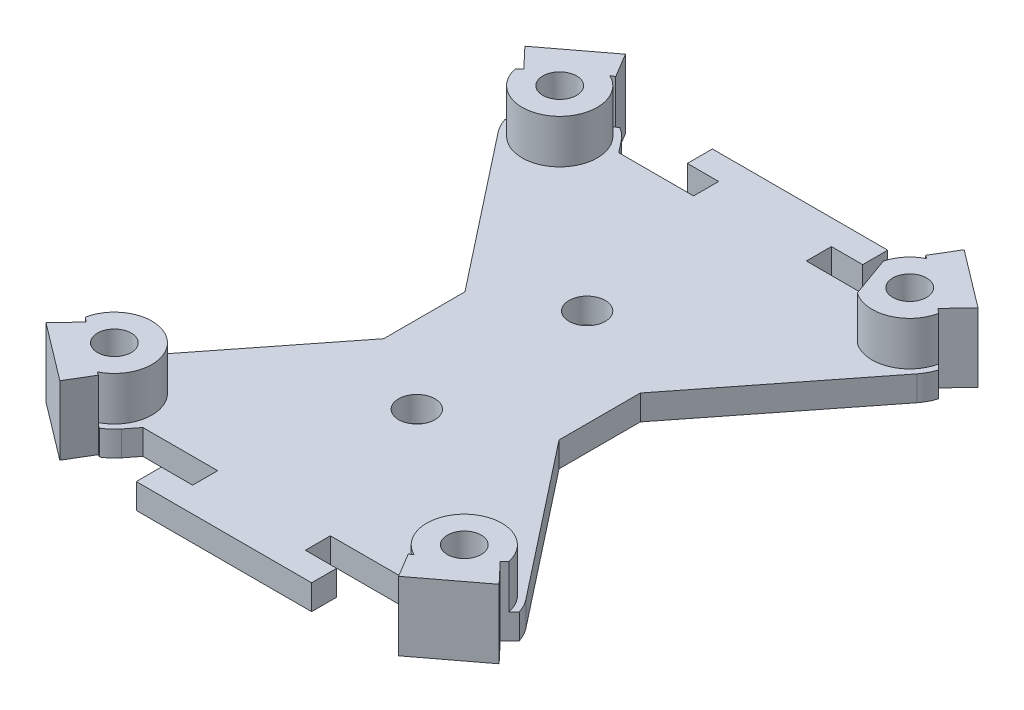
SolidWorks part; units mm, degrees
note: '?' marks a value the reader was unsure of. The reader was unsure of these and kept them because the rebuilt part matched: shared geometry of "Sketch1<3>", "Sketch1<5>".
ref_plane "Front Plane" through (0, 0, 0) normal (0, 0, 1) x (1, 0, 0)
ref_plane "Top Plane" through (0, 0, 0) normal (0, 1, 0) x (1, 0, 0)
ref_plane "Right Plane" through (0, 0, 0) normal (1, 0, 0) x (0, 0, -1)
sketch "Sketch1" plane through (0, 0, 0) normal (0, 1, 0) x (1, 0, 0)
  line L0 (0, 0) -> (0, 50000) construction
  line L1 (-13.97, 17.78) -> (13.97, 17.78) construction
  line L2 (-13.97, 17.78) -> (-13.97, -17.78) construction
  line L3 (-13.97, -17.78) -> (13.97, -17.78) construction
  line L4 (13.97, 17.78) -> (13.97, -17.78) construction
  line L5 (-13.97, 17.78) -> (13.97, -17.78) construction
  line L6 (-13.97, -17.78) -> (13.97, 17.78) construction
  line L7 (0, 0) -> (50000, 0) construction
  line L8 (0, 0) -> (18.0898, 19.1183)
  line L9 (18.0898, 19.1183) -> (13.523, 22.5805)
  line L10 (0, 0) -> (13.523, 22.5805)
  line L20 (15.8064, 20.8494) -> (16.0519, 21.1733) construction
  line L21 (-16.5, -20.62) -> (16.5, -20.62) construction
  line L22 (-16.5, -20.62) -> (-16.5, 20.62) construction
  line L23 (-16.5, 20.62) -> (16.5, 20.62) construction
  line L24 (16.5, -20.62) -> (16.5, 20.62) construction
  line L25 (-16.5, -20.62) -> (16.5, 20.62) construction
  line L26 (-16.5, 20.62) -> (16.5, -20.62) construction
  line L27 (18.0898, 19.1183) -> (18.2616, 19.2999) construction
  line L28 (0, 0) -> (13.523, -22.5805)
  line L29 (18.0898, -19.1183) -> (13.523, -22.5805)
  line L30 (0, 0) -> (18.0898, -19.1183)
  line L31 (0, 0) -> (-13.523, 22.5805)
  line L32 (-18.0898, 19.1183) -> (-13.523, 22.5805)
  line L33 (0, 0) -> (-18.0898, 19.1183)
  line L34 (0, 0) -> (-18.0898, -19.1183)
  line L35 (-18.0898, -19.1183) -> (-13.523, -22.5805)
  line L36 (0, 0) -> (-13.523, -22.5805)
  circle A0 centre (0, 0) radius 24.07
  circle A1 centre (0, 0) radius 26.5702 construction
  circle A6 centre (0, 0) radius 34.3136
  dimension "D1" = 48.14
  dimension "D8" = 53.1403
  dimension "D2" = 27.94
  dimension "D3" = 35.56
  dimension "D4" = 33
  dimension "D5" = 41.24
  dimension "D6" = 4.75
  dimension "D7" = 7.75
  dimension "D9" = 0.25
extrude "Boss-Extrude1" add sketch "Sketch1" along normal blind 2 contours L33 A0 L34 | L10 A0 L31 | L30 A0 L8 | L36 A0 L28 | L28 A0 L30 | L34 A0 L36 | L31 A0 L33 | L8 A0 L10
extrude "Boss-Extrude2" add sketch "Sketch1<3>" along normal offset from surface (5.5 mm away) 3.5 contours A0 L31 L32 L33 | A0 L8 L9 L10 | A0 L28 L29 L30 | A0 L34 L35 L36
sketch "Sketch1<3>" plane through (0, 0, 0) normal (0, 1, 0) x (1, 0, 0) same geometry as "Sketch1"
sketch "Sketch2" plane through (0, 0, 0) normal (0, 1, 0) x (1, 0, 0)
  line L4 (0, -200000) -> (0, 250000) construction
  line L5 (-200000, 0) -> (250000, 0) construction
  line L7 (0, -200000) -> (0, 250000)
  line L8 (-200000, 0) -> (250000, 0)
  circle A14 centre (13.97, 17.78) radius 3
  circle A15 centre (13.97, -17.78) radius 3
  circle A25 centre (-13.97, -17.78) radius 3
  circle A26 centre (-13.97, 17.78) radius 3
  dimension "D1" = 6
extrude "Boss-Extrude5" add sketch "Sketch2" along normal up to surface (5.5 mm away) up to face at (15.1524, 5.5, 19.9867)
ref_axis "Axis1" through (13.97, 0, -17.78) along (0, 1, 0)?
ref_axis "Axis2" through (-13.97, 0, 17.78) along (0, 1, 0)?
ref_plane "Plane1" through (0, 0, 0) normal (-0.7863, 0, -0.6178) x (-0.6178, 0, 0.7863)
sketch "Sketch3" plane through (0, 0, 0) normal (-0.7863, 0, -0.6178) x (-0.6178, 0, 0.7863)
  line L0 (19.6117, 0) -> (26.2093, 3.8091)
  line L1 (26.4079, 0) -> (6.0198, 0) construction
  line L2 (26.2093, 5.5) -> (26.2093, 0) construction
  line L3 (0, 0) -> (26.1103, 0) construction
  line L4 (19.6117, 0) -> (26.2093, 0)
  line L5 (26.2093, -3.8091) -> (26.2093, 3.8091)
  line L6 (19.6117, 5.5) -> (19.6117, 2) construction
  line L7 (0, 0) -> (0, 50000) construction
  line L8 (-26.2093, -3.8091) -> (-26.2093, 3.8091)
  line L9 (-19.6117, 0) -> (-26.2093, 0)
  line L10 (-19.6117, 0) -> (-26.2093, 3.8091)
  line L11 (-19.6117, 0) -> (-26.2093, -3.8091)
  line L12 (19.6117, 0) -> (26.2093, -3.8091)
  dimension "D1" = 30
extrude "Boss-Extrude6" [suppressed] add sketch "Sketch3" along normal up to vertex and the other way up to vertex contours L4 L12 L5 | L11 L9 L8
mirror "Mirror1" [suppressed] about plane through (0, 0, 0) normal (1, 0, 0)
extrude "Cut-Extrude3" cut sketch "Sketch1<5>" along normal through all both and the other way through all contours A6 A0 L30 L29 L28 L36 L35 L34 L33 L32 L31 L10 L9 L8
sketch "Sketch1<5>" plane through (0, 0, 0) normal (0, 1, 0) x (1, 0, 0) same geometry as "Sketch1"
hole_wizard "M2.5 Clearance Hole1" positions "Sketch6" profile "Sketch7" hole size "M2.5" standard "ANSI Metric" end condition through all
sketch "Sketch6" plane through (0, 5.5, 0) normal (0, 1, 0) x (1, 0, 0)
  point P0 (-13.97, 17.78)
  point P3 (13.97, 17.78)
  point P6 (13.97, -17.78)
  point P9 (-13.97, -17.78)
sketch "Sketch7" plane through (-13.97, 5.5, -17.78) normal (1, 0, 0) x (0, 0, 1)
  line L0 (0, 0) -> (0, 5.5005)
  line L1 (0, 5.5005) -> (1.35, 5.5005)
  line L2 (1.35, 5.5005) -> (1.35, 0)
  line L5 (1.35, 0) -> (0, 0)
  line L11 (0, -6.35) -> (0, 107.95) construction
  dimension "Thru Hole Dia." = 2.7
  dimension "Thru Hole Depth" = 5.5005
sketch "Sketch8" plane through (0, 0, 0) normal (0, -1, 0) x (1, 0, 0)
  line L0 (-13.97, 17.78) -> (13.97, -17.78) construction
  line L1 (-11.2179, 19.9424) -> (16.7221, -15.6176)
  line L2 (-16.7221, 15.6176) -> (11.2179, -19.9424)
  line L3 (13.97, 17.78) -> (-13.97, -17.78) construction
  line L4 (16.7221, 15.6176) -> (-11.2179, -19.9424)
  line L5 (11.2179, 19.9424) -> (-16.7221, -15.6176)
  line L6 (-7, -23) -> (-7, -21)
  line L7 (-7, -23) -> (7, -23)
  line L8 (0, 0) -> (0, 50000) construction
  line L9 (0, 0) -> (50000, 0) construction
  line L10 (-7, -21) -> (-4.5, -21)
  line L11 (-4.5, -21) -> (-4.5, -19)
  line L12 (-4.5, -19) -> (-10.4774, -19)
  line L13 (4.5, -19) -> (10.4774, -19)
  line L14 (4.5, -21) -> (4.5, -19)
  line L15 (7, -21) -> (4.5, -21)
  line L16 (7, -23) -> (7, -21)
  line L17 (7, 23) -> (7, 21)
  line L18 (7, 21) -> (4.5, 21)
  line L19 (4.5, 21) -> (4.5, 19)
  line L20 (4.5, 19) -> (10.4774, 19)
  line L21 (-4.5, 19) -> (-10.4774, 19)
  line L22 (-4.5, 21) -> (-4.5, 19)
  line L23 (-7, 21) -> (-4.5, 21)
  line L24 (-7, 23) -> (7, 23)
  line L25 (-7, 23) -> (-7, 21)
  line L26 (-7, -3.244) -> (-7, 3.244)
  line L27 (7, -3.244) -> (7, 3.244)
  arc A0 (-11.2179, 19.9424) -> (-16.7221, 15.6176) centre (-13.97, 17.78) ccw
  arc A1 (11.2179, -19.9424) -> (16.7221, -15.6176) centre (13.97, -17.78) ccw
  arc A2 (16.7221, 15.6176) -> (11.2179, 19.9424) centre (13.97, 17.78) ccw
  arc A3 (-16.7221, -15.6176) -> (-11.2179, -19.9424) centre (-13.97, -17.78) ccw
  circle A4 centre (0, 0) radius 34.9219
  point P4 (0, 0)
  point P9 (0, 0)
  point P27 (0, 23)
  point P32 (0, -23)
  point P39 (0, -23)
  point P50 (-7, 0)
  arc M14 (16.5433, -17.4839) -> (16.5433, 17.4839) centre (0, 0) ccw
  arc M18 (12.3669, 20.65) -> (-12.3669, 20.65) centre (0, 0) ccw
  arc M22 (-16.5433, 17.4839) -> (-16.5433, -17.4839) centre (0, 0) ccw
  arc M26 (-12.3669, -20.65) -> (12.3669, -20.65) centre (0, 0) ccw
  dimension "D1" = 7
  dimension "D2" = 7
  dimension "D3" = 23
  dimension "D4" = 2
  dimension "D5" = 2
  dimension "D6" = 2.5
  dimension "D7" = 7
extrude "Cut-Extrude4" cut sketch "Sketch8" against normal through all contours A4 A3 A0 A2 A1 M22 M18 M14 M26 | A3 L5 L2 A0 M22 | A2 A0 L1 L5 M18 | A2 L4 L1 A1 M14 | A3 A1 L2 L4 M26
ref_plane "Plane2" [suppressed] through (0, 2, 0) normal (0, 1, 0) x (1, 0, 0)
other "SurfaceCut1" [suppressed]
sketch "Sketch9" plane through (0, 0, 0) normal (0, 1, 0) x (1, 0, 0)
  line L44 (11, -14) -> (3.5, -4.4545)
  line L45 (3.5, -4.4545) -> (3.5, -14)
  line L46 (3.5, -14) -> (11, -14)
  line L47 (10.4774, -19) -> (4.5, -19) construction
  line L48 (7, -3.244) -> (16.7221, -15.6176) construction
  line L49 (0, 0) -> (0, 50000) construction
  line L50 (0, 0) -> (50000, 0) construction
  line L51 (-3.5, -14) -> (-11, -14)
  line L52 (-3.5, -4.4545) -> (-3.5, -14)
  line L53 (-11, -14) -> (-3.5, -4.4545)
  line L54 (3.5, 14) -> (11, 14)
  line L55 (3.5, 4.4545) -> (3.5, 14)
  line L56 (11, 14) -> (3.5, 4.4545)
  line L57 (-11, 14) -> (-3.5, 4.4545)
  line L58 (-3.5, 4.4545) -> (-3.5, 14)
  line L59 (-3.5, 14) -> (-11, 14)
  dimension "D1" = 5
  dimension "D2" = 3.5
  dimension "D3" = 3.5
extrude "Cut-Extrude5" [suppressed] cut sketch "Sketch9" against normal through all both and the other way through all
fillet "Fillet1" [suppressed] radius 0.5
sketch "Sketch10" plane through (0, 0, 0) normal (0, 1, 0) x (1, 0, 0)
  circle A0 centre (-0.8, -6.8) radius 1.45 construction
  circle A1 centre (-0.8, 6.8) radius 1.45 construction
  circle A2 centre (-0.8, -6.8) radius 1.45
  circle A3 centre (-0.8, 6.8) radius 1.45
extrude "Cut-Extrude6" cut sketch "Sketch10" along normal through all
sketch "Sketch11" plane through (0, 5.5, 0) normal (0, 1, 0) x (1, 0, 0)
  line L0 (4.5, -21) -> (7, -21) construction
  line L5 (-18.0898, 21) -> (18.0898, 21) construction
  line L6 (-18.0898, 21) -> (-18.0898, -21) construction
  line L7 (-18.0898, -21) -> (18.0898, -21) construction
  line L8 (10.2098, -21) -> (-10.2098, -21)
  line L9 (18.0898, 21) -> (18.0898, -21) construction
  line L10 (-18.0898, 21) -> (18.0898, -21) construction
  line L11 (-18.0898, -21) -> (18.0898, 21) construction
  line L12 (17.7398, 0) -> (10.2098, -21)
  line L13 (0, 0) -> (0, 50000)
  line L14 (0, 0) -> (50000, 0)
  line L15 (7, -3.244) -> (7, 3.244) construction
  line L16 (17.7398, 0) -> (10.2098, 21)
  line L17 (10.2098, 21) -> (-10.2098, 21)
  line L18 (-17.7398, 0) -> (-10.2098, -21)
  line L19 (-17.7398, 0) -> (-10.2098, 21)
  point P0 (0, 0)
  point P14 (7, 0)
  point P18 (0, -21)
  point P20 (0, 21)
  dimension "D1" = 0.7
  dimension "D2" = 7.88
extrude "Cut-Extrude7" cut sketch "Sketch11" against normal up to surface (3.5 mm away) contours L16 L17 L13 L14
equation "\"D1@Sketch1\"=24.57*2-1"
